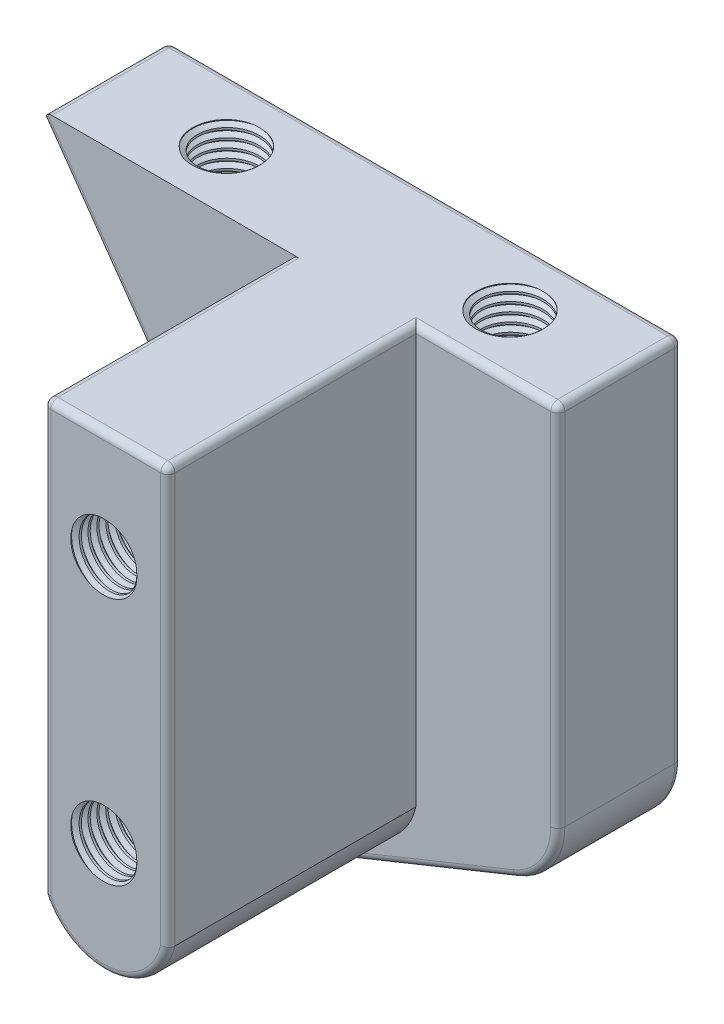
SolidWorks part; units mm, degrees
material "6061-T6 (SS)"
ref_plane "Front Plane" through (0, 0, 0) normal (0, 0, 1) x (1, 0, 0)
ref_plane "Top Plane" through (0, 0, 0) normal (0, 1, 0) x (1, 0, 0)
ref_plane "Right Plane" through (0, 0, 0) normal (1, 0, 0) x (0, 0, -1)
sketch "Sketch3" plane through (0, 0, 0) normal (0, 0, 1) x (1, 0, 0)
  line L10 (7.4354, 82.5) -> (39.813, 36.4819)
  line L11 (53.5442, -7.0017) -> (45.1315, -71.3357)
  line L12 (50.5962, -75.5631) -> (142.1175, -38.5861)
  line L13 (154, -20.9696) -> (154, 82.5)
  line L14 (154, 82.5) -> (7.4354, 82.5)
  arc A6 (53.5442, -7.0017) -> (39.813, 36.4819) centre (0, 0) ccw
  arc A7 (45.1315, -71.3357) -> (50.5962, -75.5631) centre (49.0978, -71.8543) ccw
  arc A8 (142.1175, -38.5861) -> (154, -20.9696) centre (135, -20.9696) ccw
extrude "Boss-Extrude1" add sketch "Sketch3" along normal mid plane 35
sketch "Sketch4" plane through (0, 0, 17.5) normal (0, 0, 1) x (1, 0, 0)
  line L0 (79, 82.5) -> (79, -38.745)
  line L1 (154, 82.5) -> (7.4354, 82.5) construction
  line L2 (114, 82.5) -> (114, -35.0566)
  line L3 (79, 82.5) -> (114, 82.5)
  line L4 (154, -20.9696) -> (154, 82.5) construction
  arc A0 (79, -38.745) -> (114, -35.0566) centre (95.8727, -30.9481) ccw
  dimension "D1" = 35
  dimension "D2" = 40
extrude "Boss-Extrude2" add sketch "Sketch4" along normal blind 70
fillet "Fillet1" radius 2 24 edges at (23.6242, 59.4909, -17.5) (51.4936, 16.2606, -17.5) (49.3378, -39.1687, -17.5) (46.6503, -75.0182, -17.5) (96.3569, -57.0746, -17.5) (150.7517, -31.5942, -17.5) (23.6242, 59.4909, 17.5) (51.4936, 16.2606, 17.5) (49.3378, -39.1687, 17.5) (46.6503, -75.0182, 17.5) (96.3569, -57.0746, 17.5) (150.7517, -31.5942, 17.5) (154, 30.7652, -17.5) (154, 30.7652, 17.5) (97.8207, -49.4329, 87.5) (79, 21.8775, 87.5) (114, 23.7217, 87.5) (7.4354, 82.5, 0) (134, 82.5, 17.5) (154, 82.5, 0) (80.7177, 82.5, -17.5) (79, 82.5, 52.5) (96.5, 82.5, 87.5) (114, 82.5, 52.5)
sketch "Sketch5" plane through (0, 82.5, 0) normal (0, 1, 0) x (1, 0, 0)
  line L0 (124, 17.5) -> (124, -17.5) construction
  line L1 (11.288, 17.5) -> (152, 17.5) construction
  line L2 (152, -17.5) -> (114, -17.5) construction
  line L3 (154, 15.5) -> (154, -15.5) construction
  line L4 (39.288, 40.4024) -> (39.288, -35.614) construction
  line L5 (77.0952, 17.5) -> (77.0952, -33.449) construction
  line L6 (9.288, 15.5) -> (9.288, -16.6509) construction
  circle A0 centre (124, 0) radius 8.75
  dimension "D2" = 30
  dimension "D1" = 30
extrude "Cut-Extrude1" cut sketch "Sketch5" against normal blind 20
thread "Thread2" pitch 2.5 start angle 0, offset 0, length 20, pitch 2.5, diameter 17.5
ref_plane "Plane2" through (132.75, 62.5, 0) normal (0, 0, 1) x (1, 0, 0)
sketch "Thread Profile2" plane through (132.75, 62.5, 0) normal (0, 0, 1) x (1, 0, 0)
  line L0 (0, 0) -> (0, 2.5) construction
  line L1 (0, 0) -> (1.3532, 0.7812)
  line L2 (1.3532, 0.7812) -> (1.3532, 1.0937)
  line L3 (1.3532, 1.0937) -> (0, 1.875)
  line L4 (1.3532, 0.9375) -> (0, 0.9375) construction
  line L11 (0, 0) -> (0, 1.875)
  point P2 (0, 0)
  dimension "Pitch" = 2.5
  dimension "Profile_Angle" = 60
  dimension "Profile_Land" = 0.3125
  dimension "Profile_Height" = 1.3532
pattern_linear "LPattern1" count 2 spacing 80 along (1, 0, 0) of "Cut-Extrude1", "Thread2"
sketch "Sketch14" plane through (0, 0, 87.5) normal (0, 0, 1) x (1, 0, 0)
  line L0 (96.5, 80.5) -> (94.7925, -47.5) construction
  line L1 (81, 80.5) -> (112, 80.5) construction
  line L2 (112, 82.5) -> (81, 82.5) construction
  arc A0 (81, -38.2921) -> (112, -34.8264) centre (95.8727, -30.9481) ccw construction
  circle A1 centre (96.5, 52.5) radius 8.75
  point P11 (95.1927, -17.5)
  dimension "D1" = 30
  dimension "D2" = 30
  dimension "D3" = 70
extrude "Cut-Extrude2" cut sketch "Sketch14" against normal blind 20
thread "Thread3" pitch 2.5 profile "Thread Profile3" start angle 0, offset 0, length 20, pitch 2.5, diameter 17.5
ref_plane "Plane3" through (105.25, 52.5, 67.5) normal (0, -1, 0) x (1, 0, 0)
sketch "Thread Profile3" plane through (105.25, 52.5, 67.5) normal (0, -1, 0) x (1, 0, 0)
  line L0 (0, 0) -> (0, 2.5) construction
  line L1 (0, 0) -> (1.3532, 0.7812)
  line L2 (1.3532, 0.7812) -> (1.3532, 1.0937)
  line L3 (1.3532, 1.0937) -> (0, 1.875)
  line L4 (1.3532, 0.9375) -> (0, 0.9375) construction
  line L11 (0, 0) -> (0, 1.875)
  point P2 (0, 0)
  dimension "Pitch" = 2.5
  dimension "Profile_Angle" = 60
  dimension "Profile_Land" = 0.3125
  dimension "Profile_Height" = 1.3532
sketch "Sketch17" plane through (0, 0, 87.5) normal (0, 0, 1) x (1, 0, 0)
  line L0 (96.5, 80.5) -> (96.5, -47.5233) construction
  line L1 (81, 80.5) -> (112, 80.5) construction
  arc A0 (81, -38.2921) -> (112, -34.8264) centre (95.8727, -30.9481) ccw construction
pattern_linear "LPattern4" count 2 spacing 70 along (0, -1, 0) of "Thread3", "Cut-Extrude2"
